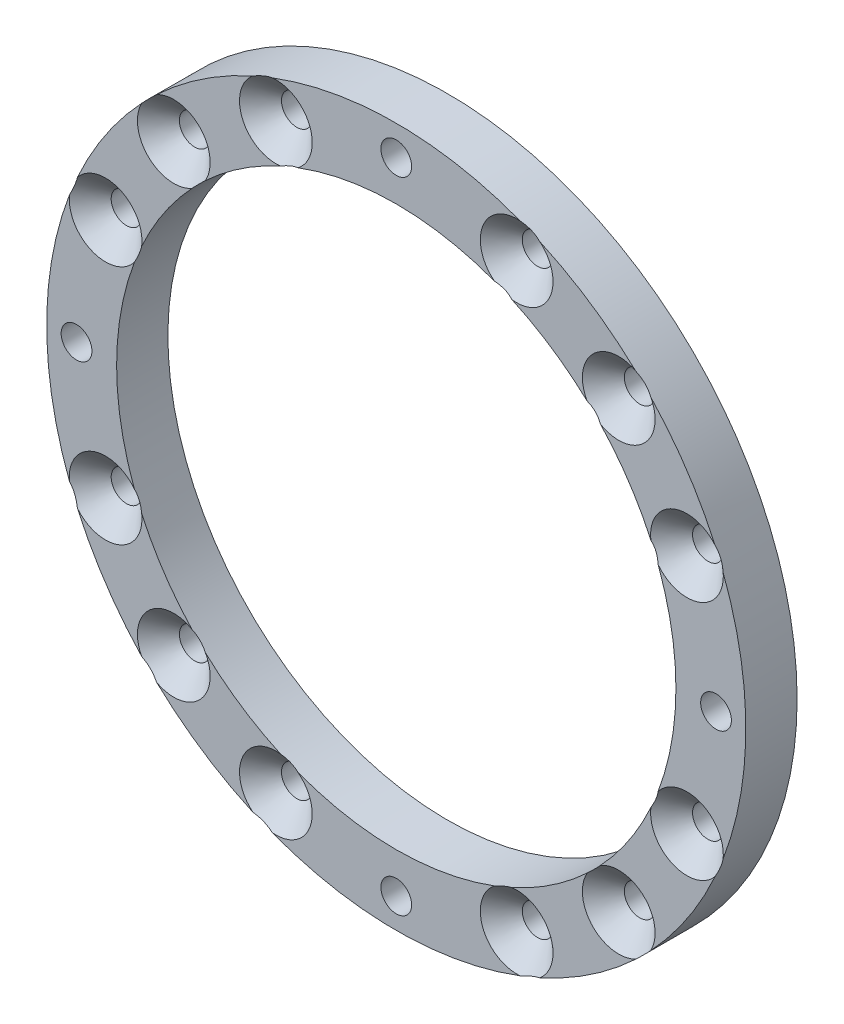
SolidWorks part; units mm, degrees
material "PET"
ref_plane "Plan de face" through (0, 0, 0) normal (0, 0, 1) x (1, 0, 0)
ref_plane "Plan de dessus" through (0, 0, 0) normal (0, 1, 0) x (1, 0, 0)
ref_plane "Plan de droite" through (0, 0, 0) normal (1, 0, 0) x (0, 0, -1)
sketch "Esquisse1" plane through (0, 0, 0) normal (0, 0, 1) x (1, 0, 0)
  circle A0 centre (0, 0) radius 37.5
  circle A1 centre (0, 0) radius 30
  dimension "D1" = 75
  dimension "D2" = 60
extrude "Boss.-Extru.1" add sketch "Esquisse1" along normal blind 5.5
sketch "Esquisse2" plane through (0, 0, 5.5) normal (0, 0, 1) x (1, 0, 0)
  line L0 (0, 34.3) -> (0, 0) construction
  line L1 (12.9156, -31.1809) -> (-12.9156, 31.1809) construction
  line L2 (-30, 0) -> (-37.5, 0) construction
  line L3 (23.8649, -23.8649) -> (-23.8649, 23.8649) construction
  line L4 (12.9156, 31.1809) -> (-12.9156, -31.1809) construction
  line L5 (-23.8649, -23.8649) -> (23.8649, 23.8649) construction
  line L6 (31.1809, 12.9156) -> (-31.1809, -12.9156) construction
  line L7 (-31.1809, 12.9156) -> (31.1809, -12.9156) construction
  circle A0 centre (0, 0) radius 34.3 construction
  circle A1 centre (0, 34.3) radius 1.65
  circle A13 centre (12.9156, 31.1809) radius 1.65
  circle A14 centre (23.8649, 23.8649) radius 1.65
  circle A15 centre (31.1809, 12.9156) radius 1.65
  circle A16 centre (34.3, 0) radius 1.65
  circle A17 centre (31.1809, -12.9156) radius 1.65
  circle A18 centre (23.8649, -23.8649) radius 1.65
  circle A19 centre (12.9156, -31.1809) radius 1.65
  circle A20 centre (0, -34.3) radius 1.65
  circle A21 centre (-12.9156, -31.1809) radius 1.65
  circle A22 centre (-23.8649, -23.8649) radius 1.65
  circle A23 centre (-31.1809, -12.9156) radius 1.65
  circle A24 centre (-34.3, 0) radius 1.65
  circle A25 centre (-31.1809, 12.9156) radius 1.65
  circle A26 centre (-23.8649, 23.8649) radius 1.65
  circle A27 centre (-12.9156, 31.1809) radius 1.65
  circle A29 centre (0, 0) radius 37.5 construction
  circle A30 centre (0, 0) radius 30 construction
  circle A31 centre (0, 0) radius 33.75 construction
  point P6 (-33.75, 0)
  point P7 (0, 0)
  point P30 (0, 0)
  point P39 (0, 0)
  dimension "D1" = 3.3
  dimension "D2" = 68.6
  dimension "D4" = 45
  dimension "D3" = 22.5
  dimension "D5" = 67.5
  dimension "D6" = 22.5
  dimension "D7" = 45
  dimension "D8" = 67.5
extrude "Enlèv. mat.-Extru.1" cut sketch "Esquisse2" against normal through all
chamfer "Chanfrein1" distance 2.25 angle 45 12 edges at (-29.5309, -12.9156, 5.5) (-22.2149, -23.8649, 5.5) (-11.2656, -31.1809, 5.5) (14.5656, -31.1809, 5.5) (25.5149, -23.8649, 5.5) (32.8309, -12.9156, 5.5) (32.8309, 12.9156, 5.5) (25.5149, 23.8649, 5.5) (14.5656, 31.1809, 5.5) (-11.2656, 31.1809, 5.5) (-22.2149, 23.8649, 5.5) (-29.5309, 12.9156, 5.5)
